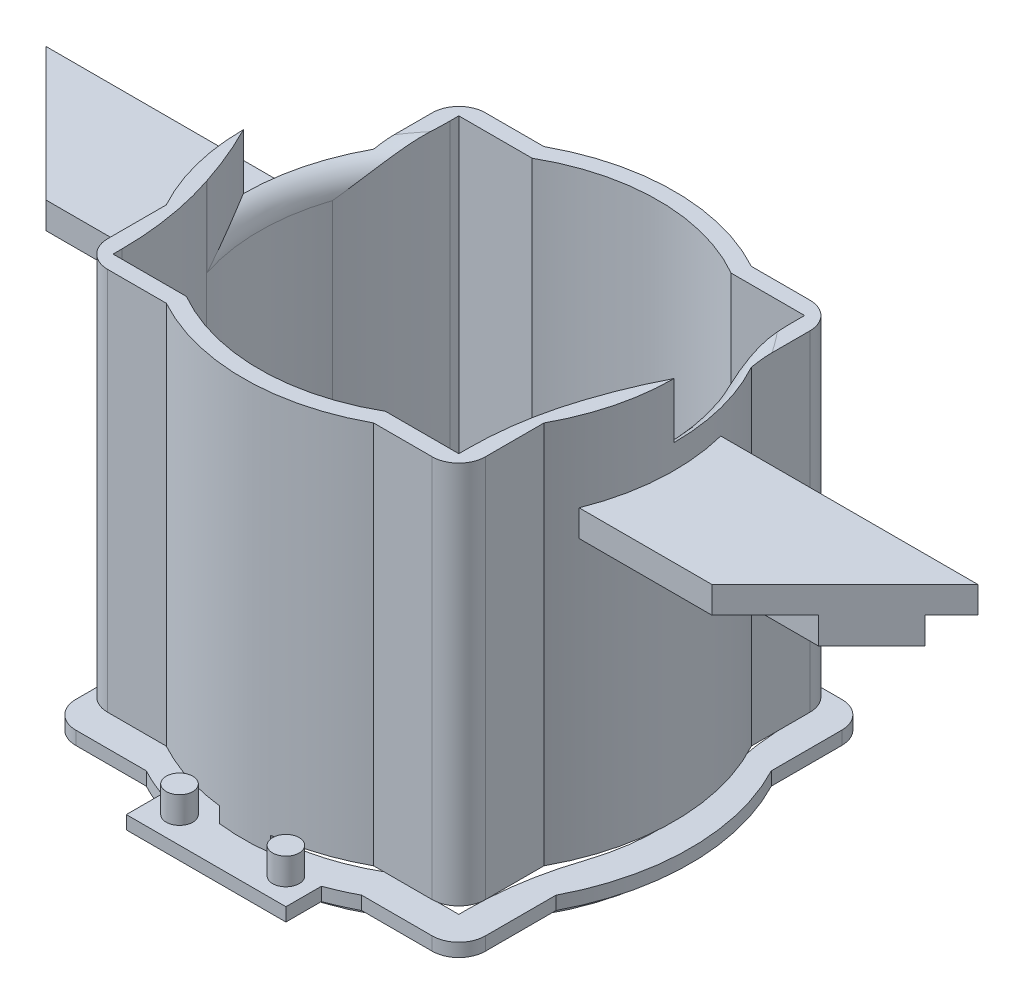
SolidWorks part; units mm, degrees
ref_plane "Front Plane" through (0, 0, 0) normal (0, 0, 1) x (1, 0, 0)
ref_plane "Top Plane" through (0, 0, 0) normal (0, 1, 0) x (1, 0, 0)
ref_plane "Right Plane" through (0, 0, 0) normal (1, 0, 0) x (0, 0, -1)
sketch "Sketch1" plane through (0, 0, 0) normal (0, 1, 0) x (1, 0, 0)
  line L0 (23.7595, 41.275) -> (41.275, 41.275)
  line L1 (-41.275, -41.275) -> (-23.7595, -41.275)
  line L2 (-41.275, -41.275) -> (-41.275, -23.7595)
  line L3 (-41.275, 41.275) -> (-23.7595, 41.275)
  line L4 (41.275, -41.275) -> (41.275, -23.7595)
  line L5 (-41.275, -41.275) -> (41.275, 41.275) construction
  line L6 (-41.275, 41.275) -> (41.275, -41.275) construction
  line L7 (41.275, 23.7595) -> (41.275, 41.275)
  line L8 (-41.275, 23.7595) -> (-41.275, 41.275)
  line L9 (23.7595, -41.275) -> (41.275, -41.275)
  line L10 (24.7569, 45.085) -> (45.085, 45.085)
  line L11 (45.085, 24.7569) -> (45.085, 45.085)
  line L12 (45.085, -45.085) -> (45.085, -24.7569)
  line L13 (24.7569, -45.085) -> (45.085, -45.085)
  line L14 (-45.085, -45.085) -> (-24.7569, -45.085)
  line L15 (-45.085, -45.085) -> (-45.085, -24.7569)
  line L16 (-45.085, 24.7569) -> (-45.085, 45.085)
  line L17 (-45.085, 45.085) -> (-24.7569, 45.085)
  arc A1 (-41.275, 23.7595) -> (-41.275, -23.7595) centre (0, 0) ccw
  arc A2 (23.7595, 41.275) -> (-23.7595, 41.275) centre (0, 0) ccw
  arc A3 (-23.7595, -41.275) -> (23.7595, -41.275) centre (0, 0) ccw
  arc A4 (41.275, -23.7595) -> (41.275, 23.7595) centre (0, 0) ccw
  arc A5 (45.085, -24.7569) -> (45.085, 24.7569) centre (0, 0) ccw
  arc A6 (-24.7569, -45.085) -> (24.7569, -45.085) centre (0, 0) ccw
  arc A7 (-45.085, 24.7569) -> (-45.085, -24.7569) centre (0, 0) ccw
  arc A8 (24.7569, 45.085) -> (-24.7569, 45.085) centre (0, 0) ccw
  point P0 (0, 0)
  dimension "D1" = 82.55
  dimension "D2" = 82.55
  dimension "D3" = 95.25
  dimension "D4" = 3.81
extrude "Boss-Extrude1" add sketch "Sketch1" along normal blind 101.6
sketch "Sketch6" plane through (0, 0, 0) normal (0, 0, 1) x (1, 0, 0)
  line L1 (-56.642, 10.033) -> (-6.096, 10.033)
  line L2 (-56.642, 10.033) -> (-56.642, 6.35)
  line L3 (-56.642, 6.35) -> (-6.096, 6.35)
  line L5 (-45.085, 0) -> (-24.7569, 0) construction
  line L8 (-6.096, 10.033) -> (-6.096, 6.35)
  line L9 (0, 0) -> (0, 21.9448) construction
  line L10 (6.096, 10.033) -> (6.096, 6.35)
  line L11 (56.642, 6.35) -> (6.096, 6.35)
  line L12 (56.642, 10.033) -> (6.096, 10.033)
  line L13 (56.642, 10.033) -> (56.642, 6.35)
  dimension "D3" = 3.683
  dimension "D1" = 6.096
  dimension "D4" = 6.35
extrude "Cut-Extrude4" cut sketch "Sketch6" against normal through all both and the other way through all
ref_plane "Plane1" through (0, 69.85, 0) normal (0, 1, 0) x (1, 0, 0)
sketch "Sketch9" plane through (0, 69.85, 0) normal (0, 1, 0) x (1, 0, 0)
  line L1 (-92.202, -6.35) -> (-51.0415, -6.35)
  line L3 (-104.902, 6.35) -> (-51.0415, 6.35)
  line L7 (-104.902, 6.35) -> (-92.202, -6.35)
  arc A0 (-45.085, 24.7569) -> (-45.085, -24.7569) centre (0, 0) ccw construction
  arc A1 (-51.0415, 6.35) -> (-51.0415, -6.35) centre (0, 0) ccw
  point P0 (0, 0)
  point P2 (-98.552, 0)
  dimension "D1" = 104.902
  dimension "D2" = 45
  dimension "D4" = 12.7
extrude "Boss-Extrude6" add sketch "Sketch9" along normal blind 12.7
sketch "Sketch11" plane through (0, 82.55, 0) normal (0, 1, 0) x (1, 0, 0)
  line L0 (-79.502, -19.05) -> (-79.502, 12.7) construction
  line L1 (-79.502, 12.7) -> (-111.252, 12.7)
  line L2 (-111.252, 12.7) -> (-79.502, -19.05)
  line L3 (-104.902, 6.35) -> (-92.202, -6.35) construction
  line L4 (-51.0415, 6.35) -> (-104.902, 6.35) construction
  line L5 (-92.202, -6.35) -> (-51.0415, -6.35) construction
  line L6 (-79.502, -19.05) -> (-47.7772, -19.05)
  line L8 (-49.8424, 12.7) -> (-79.502, 12.7)
  arc A0 (-45.085, 24.7569) -> (-45.085, -24.7569) centre (0, 0) ccw construction
  arc A2 (-49.8424, 12.7) -> (-47.7772, -19.05) centre (0, 0) ccw
  dimension "D1" = 6.35
  dimension "D2" = 12.7
extrude "Boss-Extrude8" add sketch "Sketch11" against normal blind 6.35
mirror "Mirror1" about plane through (0, 0, 0) normal (1, 0, 0) of "Boss-Extrude6", "Boss-Extrude8"
sketch "Sketch12" plane through (0, 101.6, 0) normal (0, -1, 0) x (1, 0, 0)
  line L0 (25.7155, -48.895) -> (48.895, -48.895)
  line L1 (48.895, -48.895) -> (48.895, -25.7155)
  line L2 (48.895, 25.7155) -> (48.895, 48.895)
  line L3 (48.895, 48.895) -> (25.7155, 48.895)
  line L4 (-25.7155, 48.895) -> (-48.895, 48.895)
  line L5 (-48.895, 48.895) -> (-48.895, 25.7155)
  line L6 (-48.895, -25.7155) -> (-48.895, -48.895)
  line L7 (-48.895, -48.895) -> (-25.7155, -48.895)
  line L8 (24.7569, -45.085) -> (45.085, -45.085)
  line L9 (45.085, -45.085) -> (45.085, -24.7569)
  line L10 (45.085, 24.7569) -> (45.085, 45.085)
  line L11 (45.085, 45.085) -> (24.7569, 45.085)
  line L12 (-24.7569, 45.085) -> (-45.085, 45.085)
  line L13 (-45.085, 45.085) -> (-45.085, 24.7569)
  line L14 (-45.085, -24.7569) -> (-45.085, -45.085)
  line L15 (-45.085, -45.085) -> (-24.7569, -45.085)
  line L16 (24.7569, -45.085) -> (45.085, -45.085)
  line L17 (45.085, -45.085) -> (45.085, -24.7569)
  line L18 (45.085, 24.7569) -> (45.085, 45.085)
  line L19 (45.085, 45.085) -> (24.7569, 45.085)
  line L20 (-24.7569, 45.085) -> (-45.085, 45.085)
  line L21 (-45.085, 45.085) -> (-45.085, 24.7569)
  line L22 (-45.085, -24.7569) -> (-45.085, -45.085)
  line L23 (-45.085, -45.085) -> (-24.7569, -45.085)
  arc A0 (48.895, -25.7155) -> (48.895, 25.7155) centre (0, 0) ccw
  arc A3 (25.7155, 48.895) -> (-25.7155, 48.895) centre (0, 0) ccw
  arc A4 (-48.895, 25.7155) -> (-48.895, -25.7155) centre (0, 0) ccw
  arc A5 (-25.7155, -48.895) -> (25.7155, -48.895) centre (0, 0) ccw
  arc A7 (-24.7569, -45.085) -> (24.7569, -45.085) centre (0, 0) ccw
  arc A8 (45.085, -24.7569) -> (45.085, 24.7569) centre (0, 0) ccw
  arc A9 (24.7569, 45.085) -> (-24.7569, 45.085) centre (0, 0) ccw
  arc A10 (-45.085, 24.7569) -> (-45.085, -24.7569) centre (0, 0) ccw
  arc A11 (-24.7569, -45.085) -> (24.7569, -45.085) centre (0, 0) ccw
  arc A12 (45.085, -24.7569) -> (45.085, 24.7569) centre (0, 0) ccw
  arc A13 (24.7569, 45.085) -> (-24.7569, 45.085) centre (0, 0) ccw
  arc A14 (-45.085, 24.7569) -> (-45.085, -24.7569) centre (0, 0) ccw
  dimension "D1" = 0
  dimension "D2" = 3.81
extrude "Boss-Extrude9" add sketch "Sketch12" along normal blind 3.175 from surface at 95.25 starting at face at (-30.0451, 6.35, 0)
sketch "Sketch13" plane through (0, 0, 0) normal (0, 0, 1) x (1, 0, 0)
  line L0 (24.7569, 101.6) -> (-24.7569, 101.6) construction
  line L1 (-71.4448, 101.6) -> (67.7277, 101.6)
  line L2 (-71.4448, 101.6) -> (-71.4448, 88.9)
  line L3 (-71.4448, 88.9) -> (67.7277, 88.9)
  line L4 (67.7277, 101.6) -> (67.7277, 88.9)
  dimension "D1" = 12.7
extrude "Cut-Extrude6" cut sketch "Sketch13" against normal through all
sketch "Sketch16" plane through (0, 6.35, 0) normal (0, 1, 0) x (1, 0, 0)
  line L1 (-19.05, -47.625) -> (19.05, -47.625)
  line L2 (-19.05, -47.625) -> (-19.05, -60.325)
  line L3 (-19.05, -60.325) -> (19.05, -60.325)
  line L4 (19.05, -47.625) -> (19.05, -60.325)
  line L5 (-19.05, -47.625) -> (19.05, -60.325) construction
  line L6 (-19.05, -60.325) -> (19.05, -47.625) construction
  arc A1 (-23.7595, -41.275) -> (23.7595, -41.275) centre (0, 0) ccw construction
  point P0 (0, -53.975)
  dimension "D1" = 12.7
  dimension "D2" = 38.1
extrude "Boss-Extrude13" add sketch "Sketch16" against normal blind 3.175
sketch "Sketch18" plane through (0, 6.35, 0) normal (0, 1, 0) x (1, 0, 0)
  line L0 (-19.05, -51.8566) -> (-19.05, -60.325) construction
  line L2 (-19.05, -60.325) -> (19.05, -60.325) construction
  circle A0 centre (-12.7, -53.975) radius 3.175
  point P2 (-12.7, -56.3215)
  dimension "D2" = 6.35
  dimension "D1" = 6.35
  dimension "D3" = 6.35
extrude "Boss-Extrude14" add sketch "Sketch18" along normal blind 6.35
mirror "Mirror2" about plane through (0, 0, 0) normal (1, 0, 0) of "Boss-Extrude14"
fillet "Fillet1" radius 76.2 8 edges at (41.275, 55.8165, 23.7595) (-41.275, 55.8165, 23.7595) (-41.275, 3.175, -23.7595) (-41.275, 3.175, 23.7595) (41.275, 3.175, 23.7595) (41.275, 3.175, -23.7595) (-41.275, 49.4665, -23.7595) (41.275, 49.4665, -23.7595)
fillet "Fillet2" radius 101.6 2 edges at (-47.625, 95.25, 0) (47.625, 95.25, 0)
fillet "Fillet5" radius 6.35 2 edges at (-47.6248, 88.9, -0.1363) (47.6248, 88.9, -0.1363)
fillet "Fillet6" radius 6.35 12 edges at (45.085, 1.5875, 45.085) (48.895, 4.7625, 48.895) (45.085, 1.5875, -45.085) (48.895, 4.7625, -48.895) (-45.085, 1.5875, -45.085) (-48.895, 4.7625, -48.895) (-45.085, 1.5875, 45.085) (-48.895, 4.7625, 48.895) (-45.085, 49.4665, -45.085) (45.085, 49.4665, -45.085) (45.085, 55.8165, 45.085) (-45.085, 55.8165, 45.085)
equation "\"tightTol\" = 0.005in"
equation "\"normTol\"= 0.01in"
equation "\"looseTol\"= 0.02in"
equation "\"D1@Sketch6\" = 0.250000in - \"normTol\""
equation "\"D3@Sketch6\"=\"looseTol\"+0.125000in"
